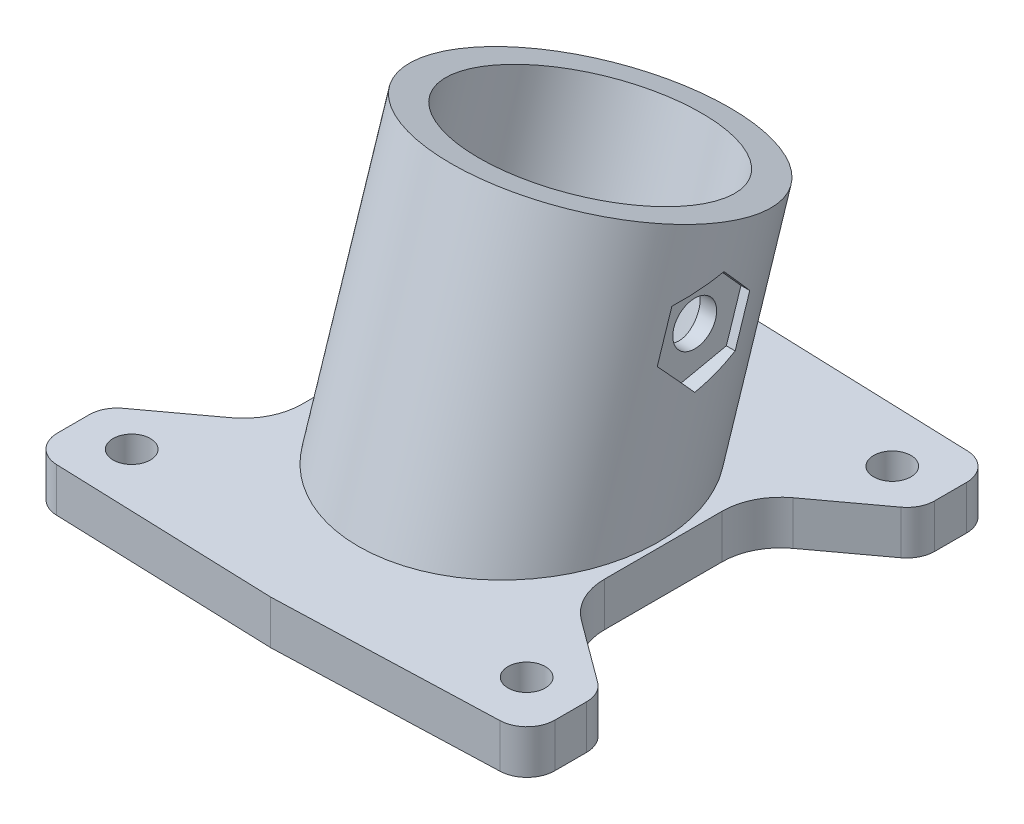
SolidWorks part; units mm, degrees
ref_plane "前基準面" through (0, 0, 0) normal (0, 0, 1) x (1, 0, 0)
ref_plane "上基準面" through (0, 0, 0) normal (0, 1, 0) x (1, 0, 0)
ref_plane "右基準面" through (0, 0, 0) normal (1, 0, 0) x (0, 0, -1)
sketch "草圖1" plane through (0, 0, 0) normal (0, 1, 0) x (1, 0, 0)
  line L0 (80.0109, 618.5863) -> (797.7278, 606.0585) construction
  line L1 (145.1902, 232.3475) -> (145.1902, 52.3475)
  line L2 (0, -66.2225) -> (0, 66.2225) construction
  line L3 (-37.6447, 0) -> (37.6447, 0) construction
  line L4 (0, 16.5) -> (15.1658, 15.9743)
  line L5 (-17, -16.5) -> (17, -16.5) construction
  line L6 (-17, -16.5) -> (-17, 16.5) construction
  line L7 (-17, 16.5) -> (17, 16.5) construction
  line L8 (17, -16.5) -> (17, 16.5) construction
  line L9 (0, 16.5) -> (0, -16.5) construction
  line L10 (-17, 0) -> (17, 0) construction
  line L11 (17, 14.0755) -> (17, 11.9023)
  line L12 (16.2276, 10.373) -> (11.9761, 7.2382)
  line L13 (10.35, 4.0188) -> (10.35, -4.0188)
  line L14 (0, 16.5) -> (-15.1658, 15.9743)
  line L15 (-17, 14.0755) -> (-17, 11.9023)
  line L16 (-16.2276, 10.373) -> (-11.9761, 7.2382)
  line L17 (-10.35, 4.0188) -> (-10.35, -4.0188)
  line L18 (16.2276, -10.373) -> (11.9761, -7.2382)
  line L19 (17, -14.0755) -> (17, -11.9023)
  line L20 (0, -16.5) -> (15.1658, -15.9743)
  line L21 (0, -16.5) -> (-15.1658, -15.9743)
  line L22 (-17, -14.0755) -> (-17, -11.9023)
  line L23 (-16.2276, -10.373) -> (-11.9761, -7.2382)
  circle A0 centre (-13.5, 12.5) radius 1.275
  circle A1 centre (-13.5, -12.5) radius 1.275
  circle A2 centre (13.5, 12.5) radius 1.275
  circle A3 centre (13.5, -12.5) radius 1.275
  arc A4 (17, -11.9023) -> (16.2276, -10.373) centre (15.1, -11.9023) ccw
  arc A5 (-17, -11.9023) -> (-16.2276, -10.373) centre (-15.1, -11.9023) cw
  arc A6 (-17, 11.9023) -> (-16.2276, 10.373) centre (-15.1, 11.9023) ccw
  arc A7 (17, 11.9023) -> (16.2276, 10.373) centre (15.1, 11.9023) cw
  arc A8 (17, 14.0755) -> (15.1658, 15.9743) centre (15.1, 14.0755) ccw
  arc A9 (-17, 14.0755) -> (-15.1658, 15.9743) centre (-15.1, 14.0755) cw
  arc A10 (-17, -14.0755) -> (-15.1658, -15.9743) centre (-15.1, -14.0755) ccw
  arc A11 (15.1658, -15.9743) -> (17, -14.0755) centre (15.1, -14.0755) ccw
  arc A12 (-10.35, 4.0188) -> (-11.9761, 7.2382) centre (-14.35, 4.0188) ccw
  arc A13 (-10.35, -4.0188) -> (-11.9761, -7.2382) centre (-14.35, -4.0188) cw
  arc A14 (11.9761, -7.2382) -> (10.35, -4.0188) centre (14.35, -4.0188) cw
  arc A15 (10.35, 4.0188) -> (11.9761, 7.2382) centre (14.35, 4.0188) cw
  point P7 (0, 0)
  point P8 (0, 0)
  point P11 (0, 0)
  point P33 (10.4017, 6.5016)
  point P36 (10.35, 0)
  point P41 (-10.35, 0)
  point P43 (17, -10.9426)
  point P46 (-17, -10.9426)
  point P49 (-17, 10.9426)
  point P52 (17, 10.9426)
  point P55 (17, 15.9108)
  point P58 (-17, 15.9108)
  point P61 (-17, -15.9108)
  point P64 (17, -15.9108)
  point P67 (-10.35, 6.0392)
  point P70 (-10.35, -6.0392)
  point P73 (10.35, -6.0392)
  point P76 (10.35, 6.0392)
  point P77 (11.9761, 7.2382)
  dimension "D4" = 2.55
  dimension "D7" = 20.7
  dimension "D8" = 1.9
  dimension "D9" = 4
  dimension "D1" = 180
  dimension "D2" = 33
  dimension "D3" = 34
  dimension "D5" = 27
  dimension "D6" = 25
extrude "填料-伸長1" add sketch "草圖1" along normal blind 3 contours L13 A15 L12 A7 L11 A8 L4 L14 A9 L15 A6 L16 A12 L17 A13 L23 A5 L22 A10 L21 L20 A11 L19 A4 L18 A14 A2 A0 A1 A3 region at (0, 0, 0)
sketch "草圖2" plane through (0, 0, 0) normal (1, 0, 0) x (0, 0, -1)
  line L0 (-10.5, 3) -> (-4.1637, 22.4962)
  line L1 (-10.373, 3) -> (-7.2382, 3) construction
  line L2 (-4.1637, 22.4962) -> (14.8569, 16.3145)
  line L3 (14.8569, 16.3145) -> (10.5297, 3)
  line L4 (4.0188, 3) -> (-4.0188, 3) construction
  line L5 (1.0185, 6.0881) -> (9.6747, 32.7226) construction
  line L6 (-10.5, 3) -> (10.5297, 3)
  point P13 (5.3466, 19.4053)
  dimension "D1" = 20.5
  dimension "D2" = 14
  dimension "D3" = 6
  dimension "D4" = 20
revolve "旋轉1" add sketch "草圖2" angle 360 mid plane about L5 region at (0, 11.2997, -2.0519)
extrude "除料-伸長2" cut sketch "草圖1<3>" against normal through all contours L13 A15 L12 A7 L11 A8 L4 L14 A9 L15 A6 L16 A12 L17 A13 L23 A5 L22 A10 L21 L20 A11 L19 A4 L18 A14 A2 A0 A1 A3 region at (0, 0, 0)
sketch "草圖1<3>" plane through (0, 0, 0) normal (0, 1, 0) x (1, 0, 0) same geometry as "草圖1"
sketch "草圖3" plane through (0, 19.1231, -6.215) normal (0, 0.951, -0.3091) x (1, 0, 0)
  circle A0 centre (0, -0.9131) radius 8
  dimension "D1" = 16
extrude "除料-伸長3" cut sketch "草圖3" against normal up to surface (19.85 mm away) up to face at (0, 3, 10.5)
sketch "草圖4" plane through (0, 0, 0) normal (1, 0, 0) x (0, 0, -1)
  line L0 (9.0562, 30.8194) -> (1.637, 7.9913) construction
  line L2 (12.9549, 16.9326) -> (-2.2617, 21.878) construction
  line L3 (14.8569, 16.3145) -> (-4.1637, 22.4962) construction
  line L5 (4.4914, 16.774) -> (1.3289, 16.102)
  line L6 (1.3289, 16.102) -> (0.3295, 13.0272)
  line L7 (0.3295, 13.0272) -> (2.4928, 10.6243)
  line L8 (2.4928, 10.6243) -> (5.6553, 11.2963)
  line L9 (5.6553, 11.2963) -> (6.6546, 14.3711)
  line L10 (6.6546, 14.3711) -> (4.4914, 16.774)
  circle A0 centre (3.4921, 13.6991) radius 1.5
  circle A1 centre (3.4921, 13.6991) radius 2.8 construction
  point P1 (4.4914, 16.774)
  point P5 (5.3466, 19.4053)
  dimension "D1" = 6
  dimension "D2" = 3
  dimension "D3" = 5.6
extrude "除料-伸長4" cut sketch "草圖4" against normal through all both and the other way through all contours A0 region at (0, 13.6991, -3.4921)
extrude "除料-伸長6" cut sketch "草圖4<3>" against normal blind 1 from offset 10
sketch "草圖4<3>" plane through (0, 0, 0) normal (1, 0, 0) x (0, 0, -1) same geometry as "草圖4"
sketch "草圖5" plane through (0, 0, 0) normal (1, 0, 0) x (0, 0, -1)
  circle A0 centre (3.4921, 13.6991) radius 3
  dimension "D1" = 6
extrude "除料-伸長8" cut sketch "草圖5" along normal blind 1 from offset 10 contours A0 offset against normal yes
